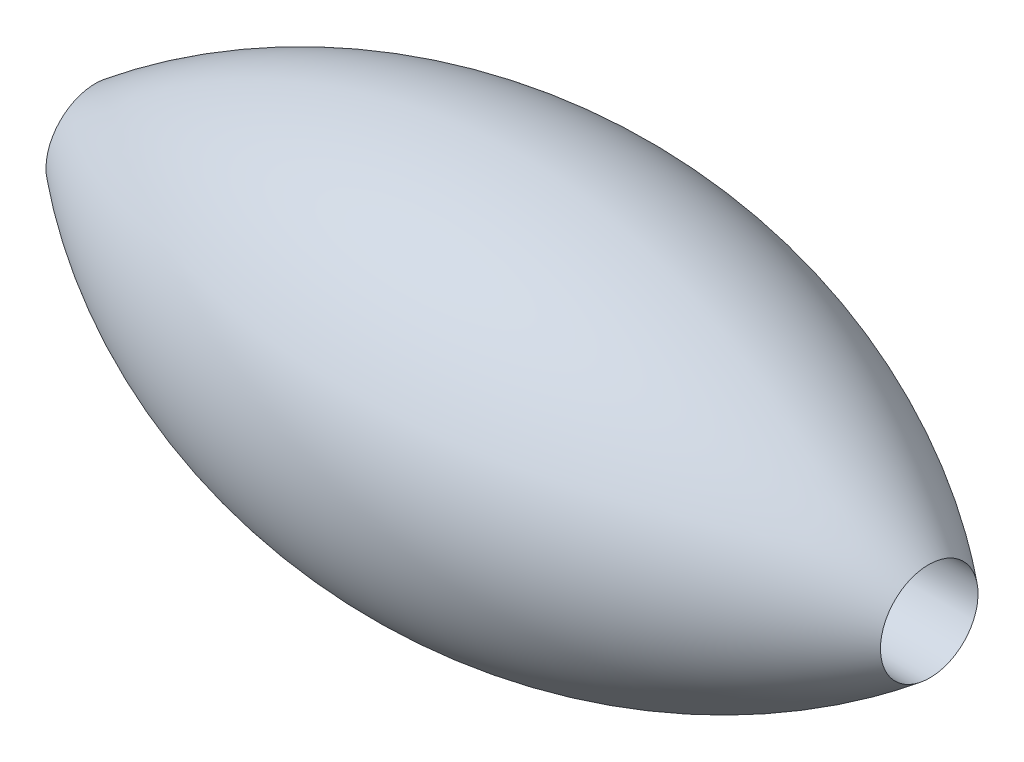
SolidWorks part; units mm, degrees
ref_plane "Front Plane" through (0, 0, 0) normal (0, 0, 1) x (1, 0, 0)
ref_plane "Top Plane" through (0, 0, 0) normal (0, 1, 0) x (1, 0, 0)
ref_plane "Right Plane" through (0, 0, 0) normal (1, 0, 0) x (0, 0, -1)
sketch "Sketch1" plane through (0, 0, 0) normal (0, 0, 1) x (1, 0, 0)
  line L0 (-7.513, -0.0072) -> (6.9926, -0.0072)
  line L1 (-0.2602, -0.0072) -> (-0.2602, -3.0072)
  arc A0 (6.9926, -0.0072) -> (-7.513, -0.0072) centre (-0.2602, 7.2599) cw
  point P7 (-0.2602, -0.0072)
  dimension "D1" = 3
revolve "Revolve1" add sketch "Sketch1" angle 360 about L0
sketch "Sketch2" plane through (0, 0, 0) normal (1, 0, 0) x (0, 0, -1)
  circle A0 centre (0, 0) radius 0.75
extrude "Cut-Extrude1" cut sketch "Sketch2" against normal through all and the other way through all
